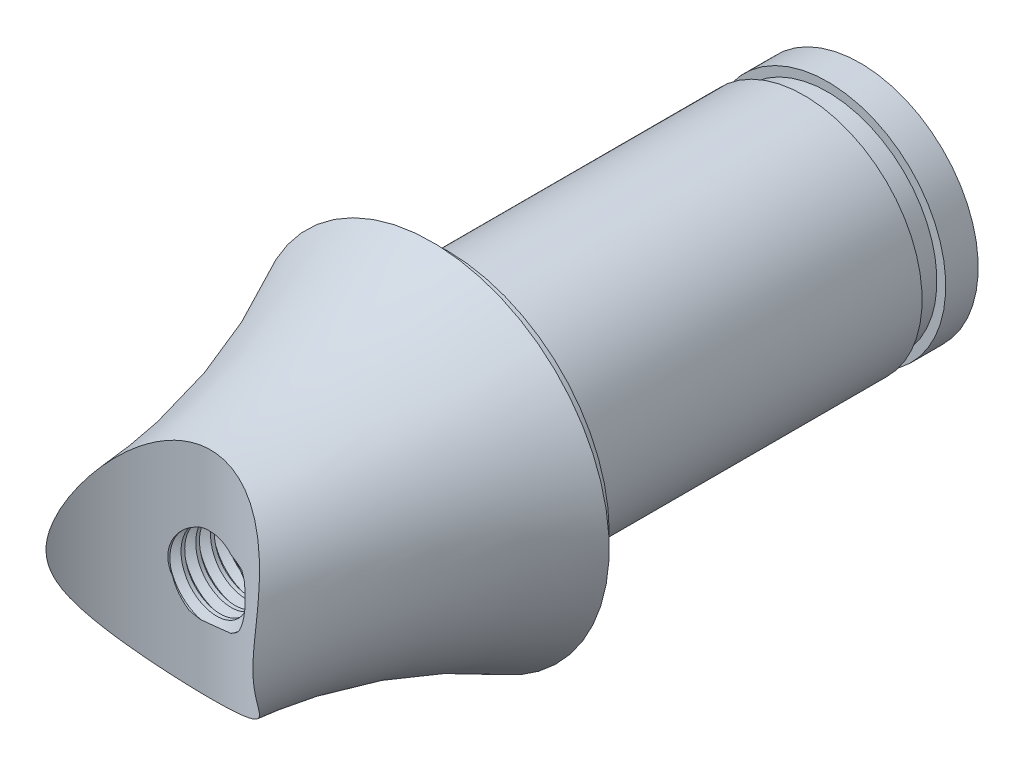
SolidWorks part; units mm, degrees
ref_plane "Front Plane" through (0, 0, 0) normal (0, 0, 1) x (1, 0, 0)
ref_plane "Top Plane" through (0, 0, 0) normal (0, 1, 0) x (1, 0, 0)
ref_plane "Right Plane" through (0, 0, 0) normal (1, 0, 0) x (0, 0, -1)
sketch "Sketch1" plane through (0, 0, 0) normal (0, 0, 1) x (1, 0, 0)
  circle A0 centre (0, 0) radius 4
  dimension "D1" = 8
extrude "Boss-Extrude1" add sketch "Sketch1" along normal blind 14.5
sketch "Sketch2" plane through (0, 0, 14.5) normal (0, 0, 1) x (1, 0, 0)
  circle A0 centre (0, 0) radius 6
  dimension "D1" = 12
extrude "Boss-Extrude2" add sketch "Sketch2" along normal blind 10
sketch "Sketch4" plane through (0, 0, 24.5) normal (0, 0, 1) x (1, 0, 0)
  circle A0 centre (0, 0) radius 1.25
  dimension "D1" = 2.5
extrude "Cut-Extrude1" cut sketch "Sketch4" against normal blind 10
thread "Thread1" pitch 0.5 method cut profile "Thread Profile1" start angle 0, offset 0, length 0, pitch 0.5, diameter 2.5
ref_plane "Plane1" through (1.25, 0, 14.5) normal (0, -1, 0) x (1, 0, 0)
sketch "Thread Profile1" plane through (1.25, 0, 14.5) normal (0, -1, 0) x (1, 0, 0)
  line L0 (0, 0) -> (0, 0.5) construction
  line L1 (0, 0) -> (0.2706, 0.1562)
  line L2 (0.2706, 0.1562) -> (0.2706, 0.2187)
  line L3 (0.2706, 0.2187) -> (0, 0.375)
  line L4 (0.2706, 0.1875) -> (0, 0.1875) construction
  line L11 (0, 0) -> (0, 0.375)
  point P2 (0, 0)
  dimension "Pitch" = 0.5
  dimension "Profile_Angle" = 60
  dimension "Profile_Land" = 0.0625
  dimension "Profile_Height" = 0.2706
sketch "Sketch8" plane through (0, 0, 0) normal (0, 0, -1) x (-1, 0, 0)
  circle A0 centre (0, 0) radius 3
  dimension "D1" = 6
extrude "Cut-Extrude2" cut sketch "Sketch8" against normal blind 2.5
sketch "Sketch9" plane through (0, 0, 0) normal (0, 0, -1) x (-1, 0, 0)
  circle A0 centre (0, 0) radius 3.7
  circle A1 centre (0, 0) radius 4 construction
  circle A2 centre (0, 0) radius 4
  dimension "D1" = 7.4
extrude "Cut-Extrude3" cut sketch "Sketch9" against normal blind 0.8 from offset 1.1 offset against normal yes
sketch "Sketch10" plane through (0, 0, 0) normal (0, 1, 0) x (1, 0, 0)
  circle A0 centre (0, -26) radius 4
  dimension "D1" = 8
  dimension "D2" = 1.5
extrude "Cut-Extrude4" cut sketch "Sketch10" against normal through all both and the other way through all
sketch "Sketch11" plane through (0, 0, 14.5) normal (0, 0, -1) x (-1, 0, 0)
  circle A0 centre (0, 0) radius 4 construction
  circle A1 centre (0, 0) radius 4
  circle A2 centre (0, 0) radius 5.5
  dimension "D1" = 11
extrude "Boss-Extrude3" add sketch "Sketch11" along normal blind 0.5
sketch "Sketch12" plane through (0, 0, 0) normal (0, 1, 0) x (1, 0, 0)
  line L0 (-6, -14.5) -> (-6, -24.5) construction
  line L1 (-6, -24.5) -> (-3.7081, -24.5) construction
  line L2 (-3.5, -24.5) -> (-3.5, -11.8174) construction
  line L3 (-6, -14.5) -> (-6, -24.5)
  line L4 (-6, -24.5) -> (-3.5, -24.5)
  line L5 (0, -11.3812) -> (0, -25.2958) construction
  arc A0 (-6, -14.5) -> (-3.5, -24.5) centre (-24.75, -24.5) cw
  dimension "D1" = 2.5
revolve "Cut-Revolve1" cut sketch "Sketch12" angle 360 about L5
